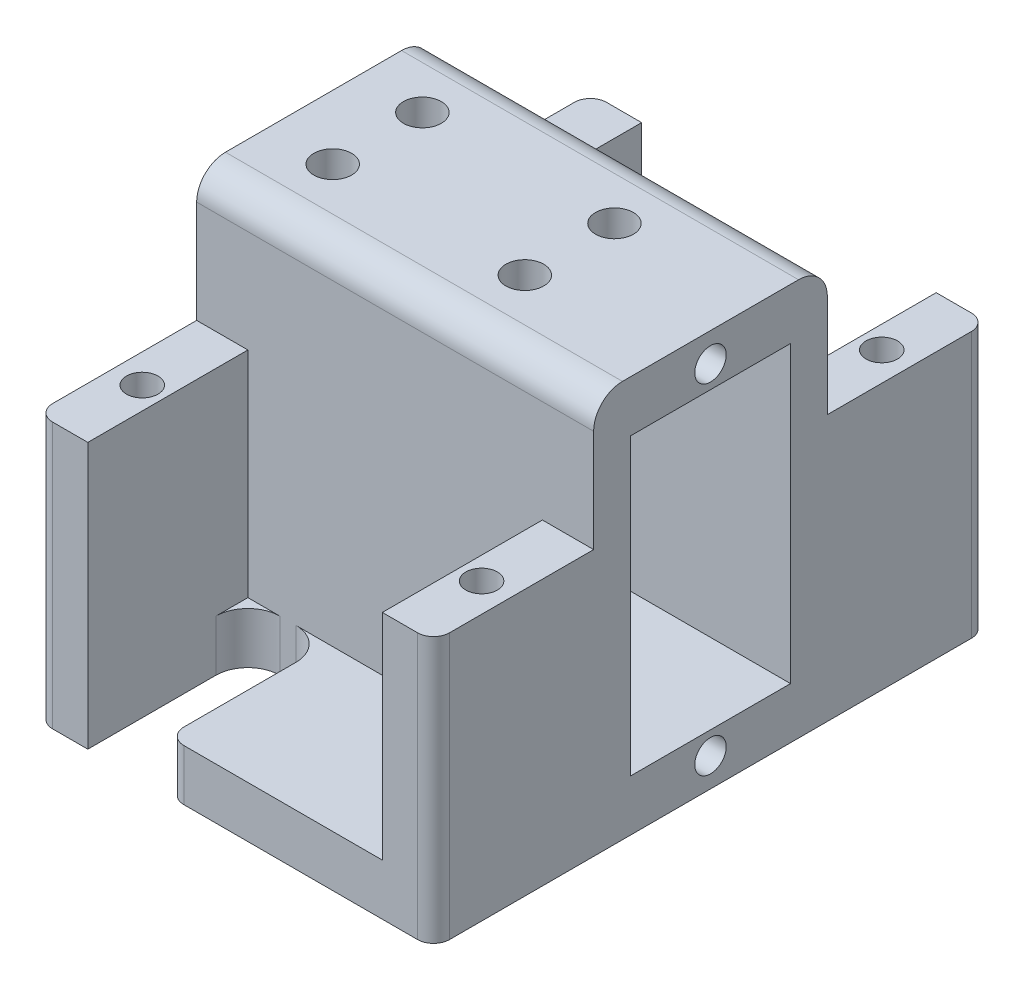
SolidWorks part; units mm, degrees
note: The reader was unsure of these and kept them because the rebuilt part matched: shared geometry of "Sketch1<5>", "Sketch1<7>", "Sketch1<9>", "Sketch1<10>", "Sketch2<3>".
ref_plane "Front Plane" through (0, 0, 0) normal (0, 0, 1) x (1, 0, 0)
ref_plane "Top Plane" through (0, 0, 0) normal (0, 1, 0) x (1, 0, 0)
ref_plane "Right Plane" through (0, 0, 0) normal (1, 0, 0) x (0, 0, -1)
sketch "Sketch1" plane through (0, 0, 0) normal (0, 1, 0) x (1, 0, 0)
  line L0 (25.146, 6.096) -> (25.146, -9.525)
  line L1 (1.778, 6.096) -> (1.778, -37.846)
  line L2 (29.21, -9.525) -> (25.146, -9.525)
  line L3 (25.146, -22.225) -> (25.146, -37.846)
  line L4 (1.778, 6.096) -> (-2.286, 6.096)
  line L5 (25.146, 6.096) -> (29.21, 6.096)
  line L6 (25.146, -37.846) -> (29.21, -37.846)
  line L7 (1.778, -37.846) -> (-2.286, -37.846)
  line L8 (29.21, -22.225) -> (25.146, -22.225)
  line L9 (29.21, -37.846) -> (29.21, -22.225)
  line L10 (29.21, 6.096) -> (29.21, -9.525)
  line L11 (-2.286, 6.096) -> (-2.286, -37.846)
  line L12 (25.146, 6.096) -> (1.778, 6.096)
  line L13 (25.146, -37.846) -> (1.778, -37.846)
  line L14 (29.21, -9.525) -> (29.21, -22.225)
  line L15 (25.146, -9.525) -> (25.146, -22.225)
  line L16 (1.778, -25.146) -> (8.128, -25.146)
  line L17 (8.128, -25.146) -> (8.128, -37.846)
  line L18 (1.778, -6.604) -> (8.128, -6.604)
  line L19 (8.128, -6.604) -> (8.128, 6.096)
  line L20 (25.146, -9.525) -> (1.778, -9.525)
  line L21 (25.146, -22.225) -> (1.778, -22.225)
  line L22 (8.128, -6.604) -> (25.146, -6.604)
  line L23 (8.128, -25.146) -> (25.146, -25.146)
  line L24 (1.778, -6.604) -> (-2.286, -6.604)
  line L25 (1.778, -25.146) -> (-2.286, -25.146)
  line L26 (25.146, -25.146) -> (29.21, -25.146)
  line L27 (25.146, -6.604) -> (29.21, -6.604)
  circle A0 centre (0, 0) radius 1.25
  circle A1 centre (26.924, 0) radius 1.25
  circle A2 centre (26.924, -31.75) radius 1.25
  circle A3 centre (0, -31.75) radius 1.25
  dimension "D1" = 2.5
  dimension "D2" = 26.924
  dimension "D3" = 31.75
  dimension "D4" = 1.778
  dimension "D5" = 1.778
  dimension "D6" = 4.064
  dimension "D7" = 6.096
  dimension "D8" = 6.096
  dimension "D9" = 12.7
  dimension "D10" = 6.35
  dimension "D11" = 12.7
extrude "Boss-Extrude1" add sketch "Sketch1" along normal blind 4.064 contours L4 L11 L7 L1 A3 A0 | L15 L0 L12 L1 L13 L3 | L10 L5 L0 L2 A1 | L2 L15 L8 L14 | L6 L9 L8 L3 A2 | L20 L0 L12 L19 L18 L1 | L3 L21 L1 L16 L17 L13 | L19 L22 L0 L12 | L23 L17 L13 L3 | A3 | L1 L25 L11 L7 A3 | L24 L1 L4 L11 A0 | L27 L0 L2 L10 | L3 L26 L9 L8
fillet "Fillet1" radius 2.54 4 edges at (8.128, 2.032, 6.604) (1.778, 2.032, 6.604) (8.128, 2.032, 25.146) (1.778, 2.032, 25.146)
extrude "Boss-Extrude2" add sketch "Sketch1<5>" along normal blind 21.082 contours L25 L1 L24 L11 | L1 L25 L11 L7 A3 | L24 L1 L4 L11 A0 | L16 L23 L3 L21 L1 | L22 L18 L1 L20 L0 | L27 L0 L2 L10 | L3 L26 L9 L8 | L26 L3 L6 L9 A2 | L0 L27 L10 L5 A1
sketch "Sketch1<5>" plane through (0, 0, 0) normal (0, 1, 0) x (1, 0, 0) same geometry as "Sketch1"
extrude "Boss-Extrude3" add sketch "Sketch1<7>" along normal blind 31.496 contours L27 L0 L2 L10 | L22 L18 L1 L20 L0 | L3 L26 L9 L8 | L21 L15 L20 L1 | L2 L15 L8 L14 | L16 L23 L3 L21 L1 | L25 L1 L24 L11
sketch "Sketch1<7>" plane through (0, 0, 0) normal (0, 1, 0) x (1, 0, 0) same geometry as "Sketch1"
extrude "Cut-Extrude1" cut sketch "Sketch1<9>" along normal blind 27.432 contours L21 L15 L20 L1 | L2 L15 L8 L14
sketch "Sketch1<9>" plane through (0, 0, 0) normal (0, 1, 0) x (1, 0, 0) same geometry as "Sketch1"
extrude "Boss-Extrude4" add sketch "Sketch1<10>" along normal blind 4.064 contours L21 L15 L20 L1 | L2 L15 L8 L14
sketch "Sketch1<10>" plane through (0, 0, 0) normal (0, 1, 0) x (1, 0, 0) same geometry as "Sketch1"
sketch "Sketch2" plane through (29.21, 0, 0) normal (1, 0, 0) x (0, 0, -1)
  line L0 (-22.225, 27.432) -> (-9.525, 27.432)
  line L1 (-9.525, 27.432) -> (-9.525, 4.064)
  line L2 (-9.525, 4.064) -> (-22.225, 4.064)
  line L3 (-22.225, 4.064) -> (-22.225, 27.432)
  line L4 (-22.225, 21.082) -> (-9.525, 21.082)
  line L5 (-9.525, 10.414) -> (-22.225, 10.414)
  circle A0 centre (-15.875, 29.21) radius 1.25
  circle A1 centre (-15.875, 2.286) radius 1.25
  point P13 (-15.875, 27.432)
  line M15 (-9.525, 4.064) -> (-22.225, 4.064)
  line M16 (-22.225, 4.064) -> (-22.225, 27.432)
  line M17 (-22.225, 27.432) -> (-9.525, 27.432)
  line M18 (-9.525, 27.432) -> (-9.525, 4.064)
  dimension "D1" = 2.5
  dimension "D2" = 1.778
  dimension "D3" = 1.778
  dimension "D4" = 6.35
  dimension "D5" = 6.35
extrude "Cut-Extrude2" cut sketch "Sketch2" against normal blind 12.7 contours A0 | A1
extrude "Cut-Extrude3" cut sketch "Sketch2<3>" against normal blind 40.132 contours L3 L4 M18 M17 | L5 M18 M16 M15
sketch "Sketch2<3>" plane through (29.21, 0, 0) normal (1, 0, 0) x (0, 0, -1) same geometry as "Sketch2"
fillet "Fillet2" radius 3.81 4 edges at (-0.254, 10.414, 22.225) (-0.254, 10.414, 9.525) (-0.254, 21.082, 22.225) (-0.254, 21.082, 9.525)
fillet "Fillet3" radius 1.27 6 edges at (8.128, 2.032, -6.096) (8.128, 2.032, 37.846) (-2.286, 10.541, -6.096) (29.21, 10.541, -6.096) (29.21, 10.541, 37.846) (-2.286, 10.541, 37.846)
sketch "Sketch3" plane through (0, 31.496, 0) normal (0, 1, 0) x (1, 0, 0)
  line L0 (-2.286, -6.604) -> (29.21, -6.604)
  line L1 (29.21, -6.604) -> (29.21, -25.146)
  line L2 (29.21, -25.146) -> (-2.286, -25.146)
  line L3 (-2.286, -25.146) -> (-2.286, -6.604)
  line L4 (-2.286, -8.763) -> (29.21, -8.763)
  line L5 (29.21, -22.987) -> (-2.286, -22.987)
  circle A0 centre (18.034, -12.319) radius 1.5
  circle A1 centre (2.794, -12.319) radius 1.5
  circle A2 centre (2.794, -19.431) radius 1.5
  circle A3 centre (18.034, -19.431) radius 1.5
  point P14 (16.0692, -11.5273)
  point P15 (18.1575, -12.319)
  point P16 (17.5052, -12.3267)
  point P24 (0.3886, -19.096)
  dimension "D1" = 3
  dimension "D2" = 14.224
  dimension "D3" = 2.159
  dimension "D4" = 3.556
  dimension "D5" = 5.08
  dimension "D6" = 3.556
  dimension "D7" = 15.24
extrude "Cut-Extrude4" cut sketch "Sketch3" against normal blind 19.304 contours A1 | A0 | A2 | A3
fillet "Fillet4" radius 2.286 2 edges at (13.462, 31.496, 6.604) (13.462, 31.496, 25.146)
